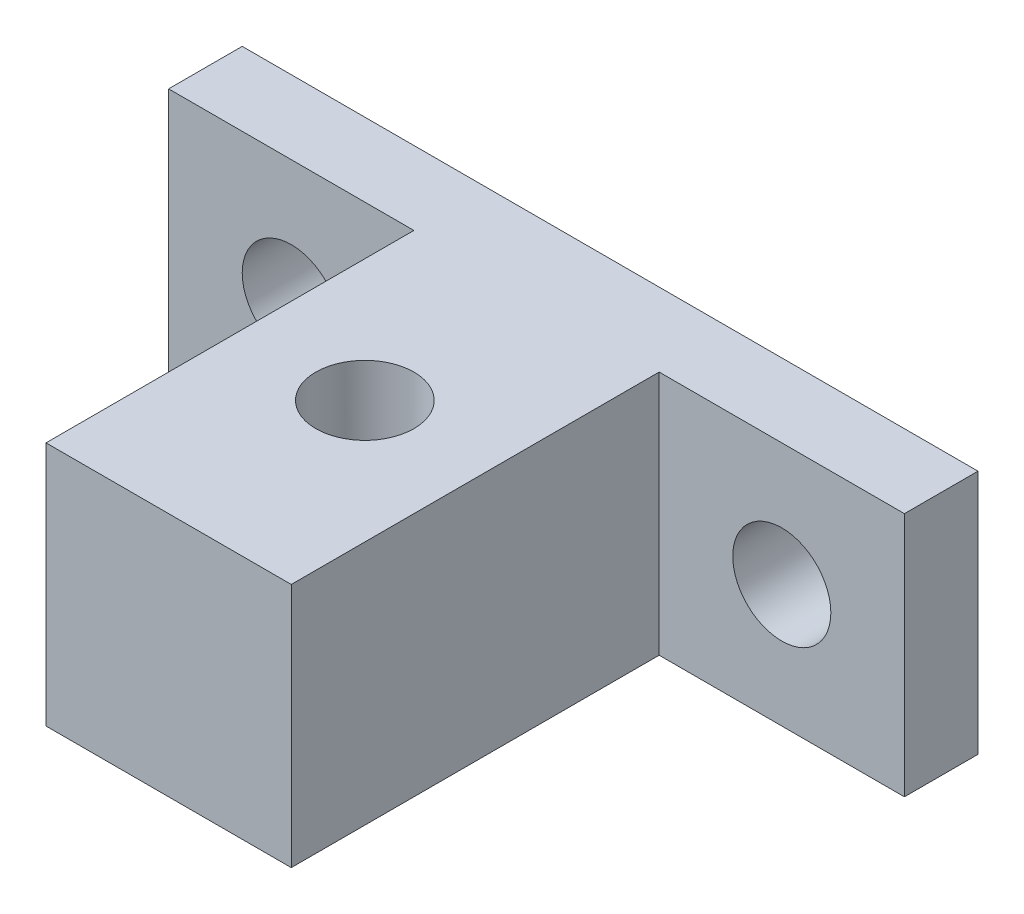
SolidWorks part; units mm, degrees
ref_plane "Front Plane" through (0, 0, 0) normal (0, 0, 1) x (1, 0, 0)
ref_plane "Top Plane" through (0, 0, 0) normal (0, 1, 0) x (1, 0, 0)
ref_plane "Right Plane" through (0, 0, 0) normal (1, 0, 0) x (0, 0, -1)
sketch "Sketch1" plane through (0, 0, 0) normal (0, 0, 1) x (1, 0, 0)
  line L0 (163.3569, -4) -> (103.3569, -4) construction
  line L1 (25, -4) -> (-5, -4)
  line L2 (25, -4) -> (25, -14)
  line L3 (25, -14) -> (-5, -14)
  line L4 (-5, -4) -> (-5, -14)
  line L5 (25, -4) -> (-5, -14) construction
  line L6 (25, -14) -> (-5, -4) construction
  line L7 (25, -9) -> (-5, -9) construction
  line L8 (10, -14) -> (10, -4) construction
  circle A0 centre (20, -9) radius 2
  circle A1 centre (0, -9) radius 2
  dimension "D3" = 4
  dimension "D4" = 10
  dimension "D1" = 10
  dimension "D2" = 30
extrude "Boss-Extrude1" add sketch "Sketch1" along normal blind 3
sketch "Sketch2" plane through (0, 0, 3) normal (0, 0, 1) x (1, 0, 0)
  line L0 (25, -4) -> (-5, -4) construction
  line L1 (15, -4) -> (5, -4)
  line L2 (15, -4) -> (15, -14)
  line L3 (15, -14) -> (5, -14)
  line L4 (5, -4) -> (5, -14)
  line L5 (15, -4) -> (5, -14) construction
  line L6 (15, -14) -> (5, -4) construction
  line L7 (-5, -14) -> (25, -14) construction
  line L9 (-5, -4) -> (-5, -14) construction
  line L10 (25, -14) -> (25, -4) construction
  point P4 (10, -9)
  dimension "D1" = 10
  dimension "D2" = 10
extrude "Boss-Extrude2" add sketch "Sketch2" along normal blind 15
sketch "Sketch3" plane through (0, -4, 0) normal (0, 1, 0) x (1, 0, 0)
  line L0 (5, -18) -> (5, -3) construction
  line L1 (10, -6.074) -> (6.6, -8.037)
  line L2 (6.6, -8.037) -> (6.6, -11.963)
  line L3 (6.6, -11.963) -> (10, -13.926)
  line L4 (10, -13.926) -> (13.4, -11.963)
  line L5 (13.4, -11.963) -> (13.4, -8.037)
  line L6 (13.4, -8.037) -> (10, -6.074)
  line L7 (25, 0) -> (-5, 0) construction
  circle A0 centre (10, -10) radius 3.4 construction
  circle A1 centre (10, -10) radius 2
  dimension "D3" = 10
  dimension "D4" = 4
  dimension "D1" = 6.8
  dimension "D2" = 5
extrude "Cut-Extrude1" cut sketch "Sketch3" along normal blind 5 from surface starting at face at (10, -14, 6)
extrude "Cut-Extrude2" cut sketch "Sketch3<2>" against normal through all both and the other way through all contours A1 region at (10, -4, 10)
sketch "Sketch3<2>" plane through (0, -4, 0) normal (0, 1, 0) x (1, 0, 0) same geometry as "Sketch3"
